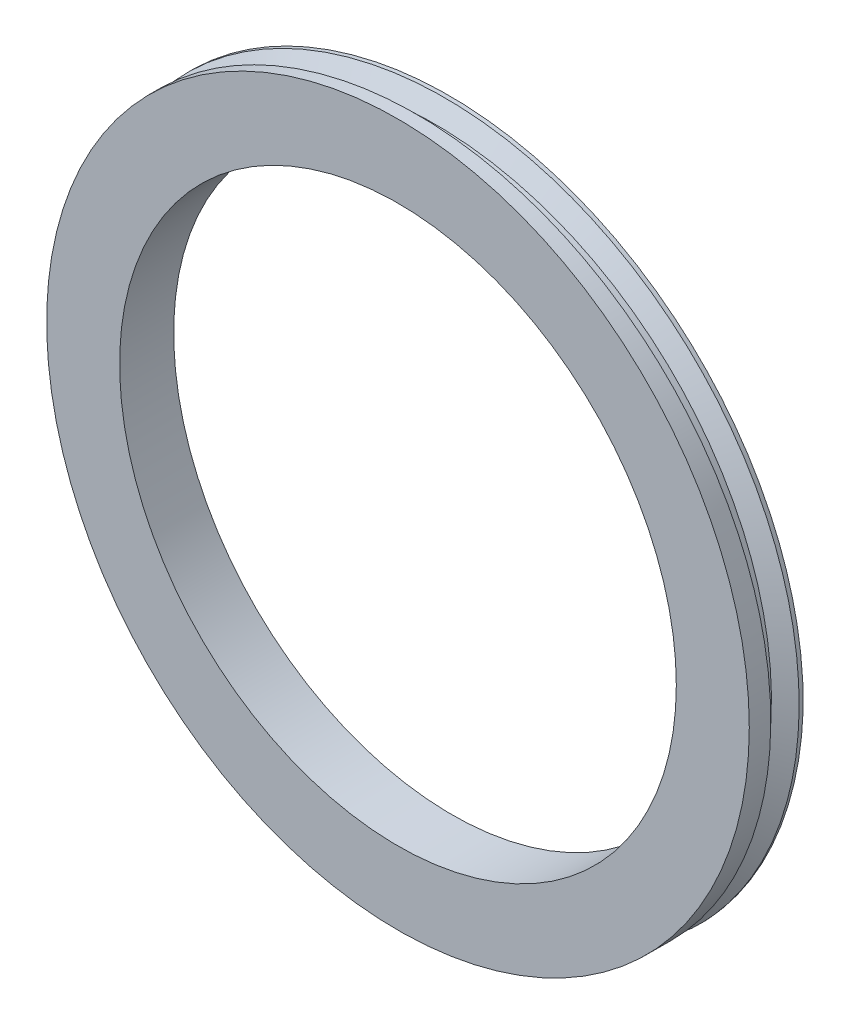
SolidWorks part; units mm, degrees
ref_plane "Front Plane" through (0, 0, 0) normal (0, 0, 1) x (1, 0, 0)
ref_plane "Top Plane" through (0, 0, 0) normal (0, 1, 0) x (1, 0, 0)
ref_plane "Right Plane" through (0, 0, 0) normal (1, 0, 0) x (0, 0, -1)
sketch "Sketch1" plane through (0, 0, 0) normal (0, 0, 1) x (1, 0, 0)
  circle A0 centre (0, 0) radius 51.5
  circle A1 centre (0, 0) radius 65
extrude "Boss-Extrude1" add sketch "Sketch1" along normal blind 10
thread "Thread1" pitch 6 method cut profile "Thread Profile1" start angle 2, offset 1, length 0, pitch 6, diameter 130
ref_plane "Plane1" through (-64.9604, 2.2685, 9) normal (-0.0349, -0.9994, 0) x (-0.9994, 0.0349, 0)
sketch "Thread Profile1" plane through (-64.9604, 2.2685, 9) normal (-0.0349, -0.9994, 0) x (-0.9994, 0.0349, 0)
  line L0 (0, 0) -> (0, 6) construction
  line L11 (0, 0) -> (0, 5.25)
  line L12 (0, 5.25) -> (-3.2476, 3.375)
  line L13 (-3.2476, 3.375) -> (-3.2476, 1.875)
  line L15 (-3.2476, 1.875) -> (0, 0)
  line L17 (-3.2476, 2.625) -> (0, 2.625) construction
  point P2 (0, 0)
  dimension "Pitch" = 6
  dimension "Profile_Angle" = 60
  dimension "Profile_Land" = 1.5
  dimension "Profile_Height" = 3.2476
sketch "Sketch10" plane through (0, 0, 0) normal (0.0349, 0.9994, 0) x (0.9994, -0.0349, 0)
  circle A0 centre (-63.3874, -6.374) radius 1
extrude "Cut-Extrude1" cut sketch "Sketch10" against normal blind 21
